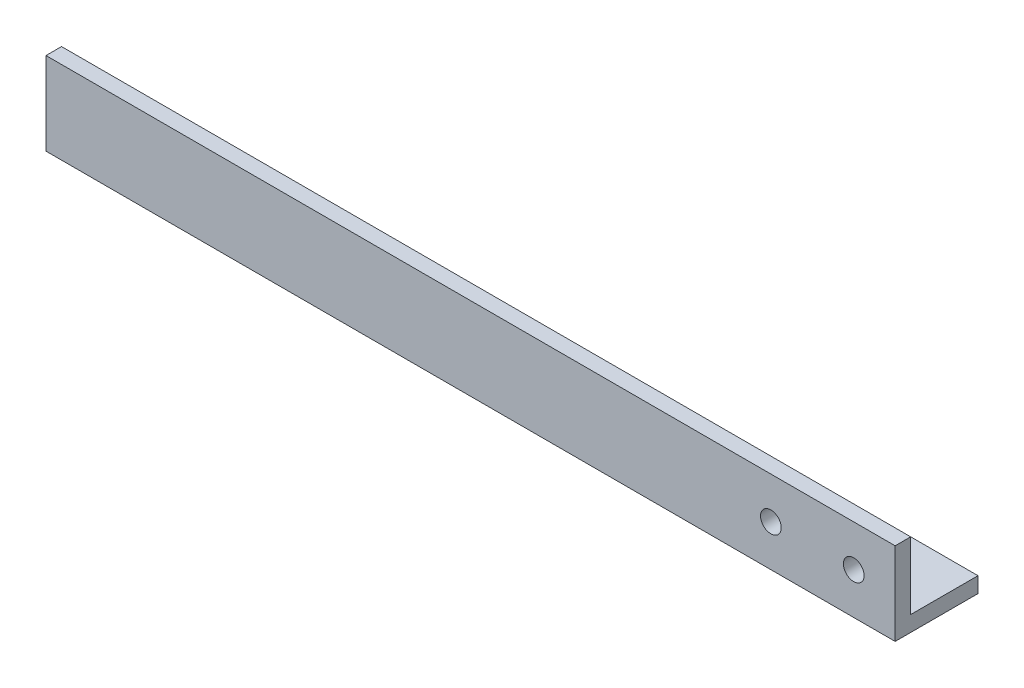
SolidWorks part; units mm, degrees
material "6061 Alloy"
ref_plane "Front Plane" through (0, 0, 0) normal (0, 0, 1) x (1, 0, 0)
ref_plane "Top Plane" through (0, 0, 0) normal (0, 1, 0) x (1, 0, 0)
ref_plane "Right Plane" through (0, 0, 0) normal (1, 0, 0) x (0, 0, -1)
sketch "Sketch1" plane through (0, 0, 0) normal (1, 0, 0) x (0, 0, -1)
  line L0 (0, 0) -> (0, -25.4)
  line L1 (0, -25.4) -> (25.4, -25.4)
  line L2 (25.4, -25.4) -> (25.4, -20.6375)
  line L3 (25.4, -20.6375) -> (4.7625, -20.6375)
  line L4 (4.7625, -20.6375) -> (4.7625, 0)
  line L5 (4.7625, 0) -> (0, 0)
  dimension "D1" = 4.7625
  dimension "D2" = 4.7625
  dimension "D3" = 25.4
  dimension "D4" = 25.4
extrude "Boss-Extrude1" add sketch "Sketch1" along normal blind 260.35
sketch "Sketch2" plane through (0, -20.6375, 0) normal (0, 1, 0) x (1, 0, 0)
  line L1 (0, 25.4) -> (0, 4.7625) construction
  line L2 (260.35, 0) -> (0, 0) construction
  circle A0 centre (9.525, 11.1125) radius 3.175
  circle A1 centre (19.05, 17.4625) radius 3.175
  dimension "D1" = 11.1125
  dimension "D2" = 17.4625
  dimension "D3" = 19.05
  dimension "D4" = 6.35
  dimension "D5" = 6.35
  dimension "D6" = 9.525
extrude "Cut-Extrude1" cut sketch "Sketch2" against normal up to next
sketch "Sketch3" plane through (0, -25.4, 0) normal (0, -1, 0) x (1, 0, 0)
  circle A0 centre (184.0953, -13.4704) radius 3.175 construction
  circle A1 centre (184.0953, -13.4704) radius 3.175
extrude "Cut-Extrude2" cut sketch "Sketch3" against normal up to next
sketch "Sketch6" plane through (0, 0, 0) normal (0, 0, 1) x (1, 0, 0)
  circle A0 centre (222.25, -12.7) radius 3.175 construction
  circle A1 centre (247.65, -12.7) radius 3.175 construction
  circle A2 centre (222.25, -12.7) radius 3.175
  circle A3 centre (247.65, -12.7) radius 3.175
extrude "Cut-Extrude3" cut sketch "Sketch6" against normal up to next
